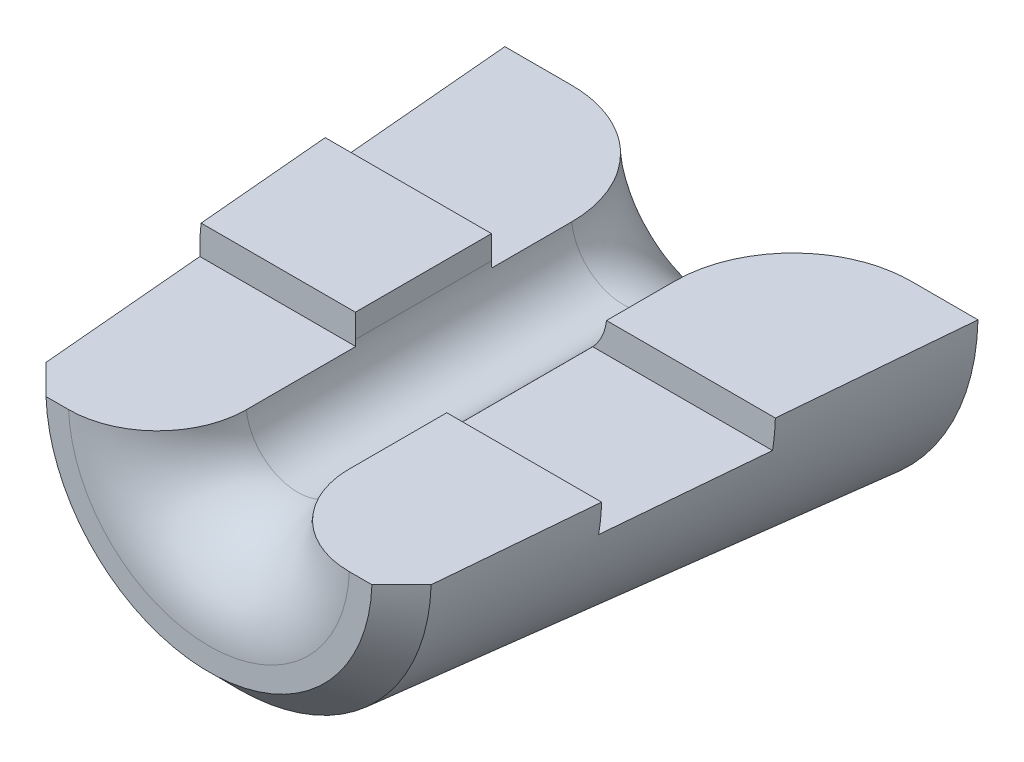
SolidWorks part; units mm, degrees
ref_plane "Front" through (0, 0, 0) normal (0, 0, 1) x (1, 0, 0)
ref_plane "Top" through (0, 0, 0) normal (0, 1, 0) x (1, 0, 0)
ref_plane "Right" through (0, 0, 0) normal (1, 0, 0) x (0, 0, -1)
sketch "Sketch2" plane through (0, 0, 0) normal (1, 0, 0) x (0, 0, -1)
  line L0 (0, 0) -> (-18, 0)
  line L1 (-18, 0) -> (-18, 5.5127)
  line L2 (-18, 5.5127) -> (-17, 6.5127)
  line L3 (-17, 6.5127) -> (0, 8)
  line L5 (0, 8) -> (0, 0)
  line L9 (-18, 5.5127) -> (-18, 6.4252) construction
  line L10 (-18, 6.4252) -> (-17, 6.5127) construction
  line L13 (-18, 0) -> (-20.4063, 0) construction
  point P3 (0, 0)
  dimension "D1" = 45
  dimension "D2" = 16
  dimension "D3" = 1
  dimension "D5" = 18
  dimension "D7" = 5
revolve "Body Revolve1" add sketch "Sketch2" angle 360 about L13
sketch "Sketch3" plane through (0, 0, 0) normal (0, 0, 1) x (1, 0, 0)
  circle A0 centre (0, 0) radius 1.75
  dimension "D1" = 3.5
extrude "Wire Hole Cut" cut sketch "Sketch3" along normal through all
fillet "Front Strain Fillet" radius 3 1 edges at (1.75, 0, 18)
fillet "Rear Strain Fillet" radius 4 1 edges at (1.75, 0, 0)
sketch "Sketch5" plane through (0, 0, 0) normal (1, 0, 0) x (0, 0, -1)
  line L0 (-18, 0) -> (-11.5, 0)
  line L2 (-11.5, 0) -> (-6.5, 0) construction
  line L3 (-6.5, 0) -> (0, 0)
  line L4 (-11.5, 0) -> (-11.5, 1)
  line L5 (-11.5, 1) -> (-6.5, 1)
  line L6 (-6.5, 1) -> (-6.5, 0)
  line L7 (-18, 5.5127) -> (-18, 6.4252) construction
  dimension "D1" = 1
  dimension "D2" = 5
extrude "Split Cut 1" cut sketch "Sketch5" against normal through all thin thin type one direction wall 0.2
sketch "Sketch7" plane through (0, 0, 0) normal (1, 0, 0) x (0, 0, -1)
  line L0 (-18, 0) -> (-11.5, 0)
  line L1 (-11.5, 0) -> (-11.5, -1)
  line L2 (-11.5, -1) -> (-6.5, -1)
  line L3 (-6.5, -1) -> (-6.5, 0)
  line L4 (-6.5, 0) -> (0, 0)
  line L5 (-11.5, 0) -> (-11.5, 1) construction
extrude "Split Cut 2" cut sketch "Sketch7" along normal through all thin thin type one direction wall 0.2
sketch "Sketch6" plane through (0, 0, 0) normal (0, 0, 1) x (1, 0, 0)
  line L0 (-1.75, 0) -> (-1.75, 2)
  line L2 (-1.75, 2) -> (1.75, 2)
  line L3 (1.75, 2) -> (1.75, 0)
  circle A0 centre (0, 0) radius 1.75 construction
  arc A1 (-1.75, 0) -> (1.75, 0) centre (0, 0) ccw
  dimension "D1" = 2
extrude "Wire Insert Notch" cut sketch "Sketch6" along normal through all
